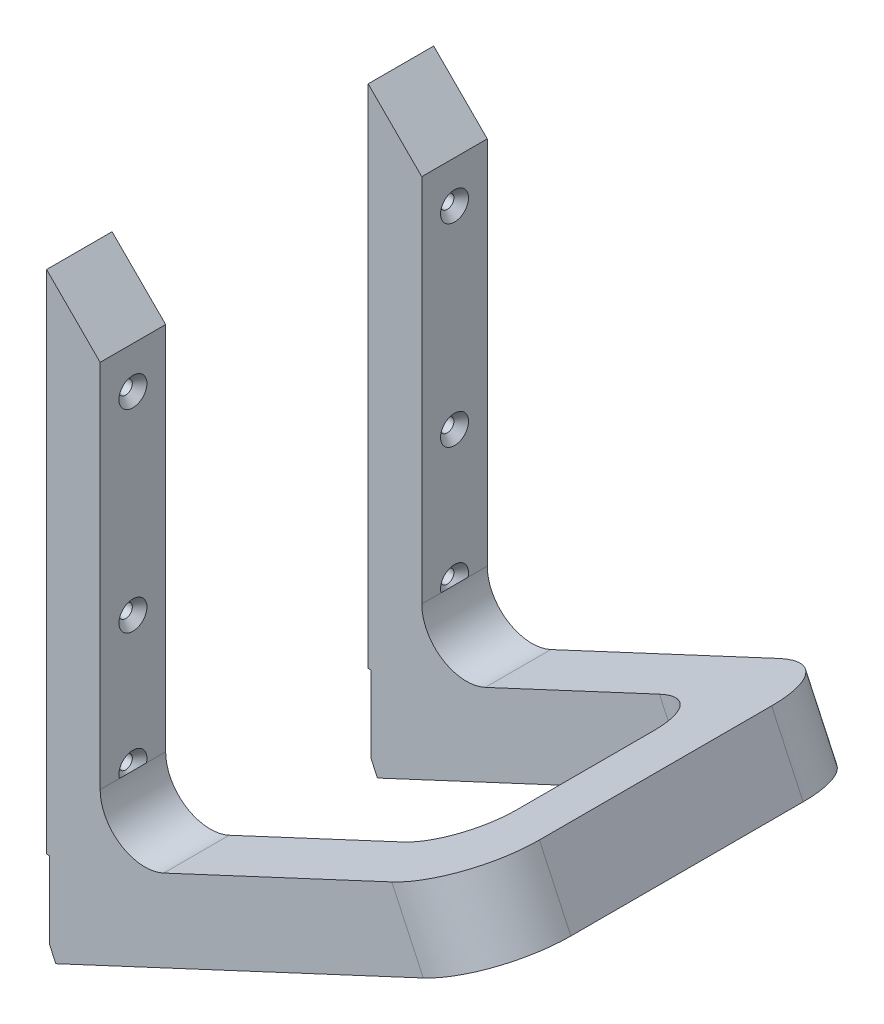
SolidWorks part; units mm, degrees
ref_plane "Ebene vorne" through (0, 0, 0) normal (0, 0, 1) x (1, 0, 0)
ref_plane "Ebene oben" through (0, 0, 0) normal (0, 1, 0) x (1, 0, 0)
ref_plane "Ebene rechts" through (0, 0, 0) normal (1, 0, 0) x (0, 0, -1)
sketch "Skizze1" plane through (0, 0, 0) normal (0, 0, 1) x (1, 0, 0)
  line L0 (0, 0) -> (18, 0)
  line L1 (18, 0) -> (18, -142.2665)
  line L2 (39.3393, -155.8611) -> (115.9374, -120.1428)
  line L3 (115.9374, -120.1428) -> (126.5028, -142.8005)
  line L4 (126.5028, -142.8005) -> (3.1131, -200.3381)
  line L5 (1, -175) -> (1, -170)
  line L6 (1, -170) -> (0, -170)
  line L7 (0, -170) -> (0, 0)
  line L8 (1, -175) -> (1, -195.8065)
  line L9 (1, -195.8065) -> (3.1131, -200.3381)
  arc A0 (18, -142.2665) -> (39.3393, -155.8611) centre (33, -142.2665) ccw
  point P6 (0, 0)
  point P14 (7.3474, -183.7282)
  dimension "D6" = 15
  dimension "D7" = 136.1455
  dimension "D2" = 18
  dimension "D3" = 65
  dimension "D4" = 25
  dimension "D5" = 5
  dimension "D8" = 170
  dimension "D9" = 5
  dimension "D10" = 10
  dimension "D11" = 1
extrude "Aufsatz-Linear austragen1" add sketch "Skizze1" along normal blind 22
sketch "Skizze2" plane through (77.2899, -165.7488, 0) normal (0.4226, -0.9063, 0) x (0.9063, 0.4226, 0)
  line L0 (-81.8451, 0) -> (54.3004, 0) construction
  line L1 (54.3004, 22) -> (54.3004, 65)
  line L2 (54.3004, 65) -> (80.3004, 65)
  line L3 (80.3004, 65) -> (80.3004, 26)
  line L8 (-81.8451, 0) -> (54.3004, 0)
  line L9 (54.3004, 0) -> (54.3004, 22)
  line L10 (54.3004, 22) -> (-81.8451, 22)
  line L11 (-81.8451, 22) -> (-81.8451, 0)
  line L13 (54.3004, 0) -> (54.3004, 22)
  line L14 (-81.8451, 22) -> (-81.8451, 0)
  arc A0 (54.3004, 0) -> (80.3004, 26) centre (54.3004, 26) ccw
  point P12 (54.3004, 11)
  dimension "D1" = 26
  dimension "D3" = 54
  dimension "D2" = 0
extrude "Aufsatz-Linear austragen2" add sketch "Skizze2" against normal up to surface (25 mm away) contours L13 L1 L2 L3 A0 up to face at (77.6383, -138.0019, 11)
ref_plane "Ebene3" through (0, 0, 65) normal (0, 0, 1) x (1, 0, 0)
sketch "Skizze3" plane through (18, 0, 0) normal (1, 0, 0) x (0, 0, -1)
  line L0 (-22, 0) -> (0, 0) construction
  point P0 (-11, -141)
  point P1 (-11, -32)
  point P4 (-11, 0)
  point P6 (-11, -97)
  dimension "D1" = 109
  dimension "D2" = 32
  dimension "D3" = 65
hole_wizard "Formsenkung für M4 Linsensenkschraube mit Schlitz1" positions "Skizze4" profile "Skizze6" countersink size "M4" standard "DIN" end condition through all
sketch "Skizze4" plane through (18, 0, 0) normal (1, 0, 0) x (0, 0, -1)
  point P0 (-11, -32)
  point P3 (-11, -141)
  point P7 (-11, -97)
sketch "Skizze6" plane through (18, -32, 11) normal (0, 1, 0) x (0, 0, -1)
  line L0 (0, 0) -> (0, 18)
  line L1 (0, 18) -> (2.25, 18)
  line L2 (2.25, 18) -> (2.25, 2.45)
  line L3 (2.25, 2.45) -> (4.7, 0)
  line L5 (4.7, 0) -> (0, 0)
  line L6 (-2.25, 2.45) -> (-4.7, 0) construction
  line L11 (0, -6.35) -> (0, 107.95) construction
  dimension "Bohrerdurchmesser" = 4.5
  dimension "Bohrungstiefe" = 18
  dimension "Senkdurchmesser (Oben)" = 9.4
  dimension "Senkwinkel (Oben)" = 90
mirror "Spiegeln4" about plane through (86.3511, -56.6948, 65) normal (0, 0, -1) of "Aufsatz-Linear austragen2"
mirror "Spiegeln5" about plane through (0, 0, 65) normal (0, 0, 1) of "Formsenkung für M4 Linsensenkschraube mit Schlitz1", "Aufsatz-Linear austragen1"
fillet "Verrundung1" radius 20 2 edges at (121.2201, -131.4716, 22) (121.2201, -131.4716, 108)
chamfer "Fase1" distance 18 angle 45 2 edges at (18, 0, 119) (18, 0, 11)
